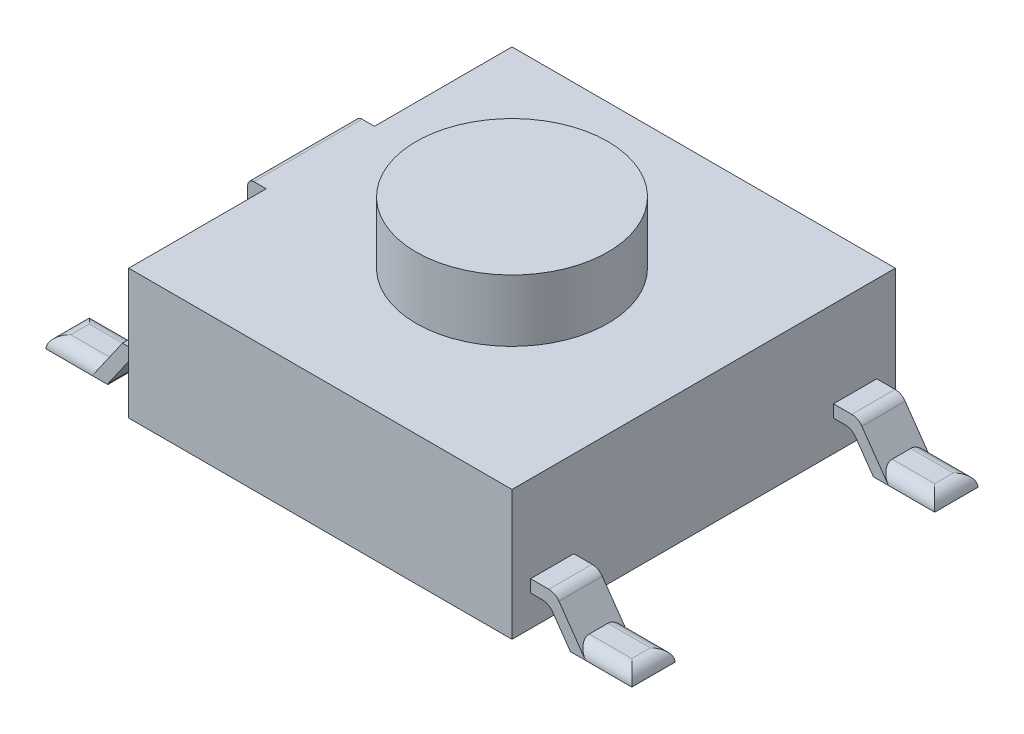
SolidWorks part; units mm, degrees
ref_plane "Plan de face" through (0, 0, 0) normal (0, 0, 1) x (1, 0, 0)
ref_plane "Plan de dessus" through (0, 0, 0) normal (0, 1, 0) x (1, 0, 0)
ref_plane "Plan de droite" through (0, 0, 0) normal (1, 0, 0) x (0, 0, -1)
sketch "Esquisse1" plane through (0, 0, 0) normal (0, 1, 0) x (1, 0, 0)
  line L1 (0, 0) -> (6.2, 0)
  line L2 (0, 0) -> (0, 6.2)
  line L3 (0, 6.2) -> (6.2, 6.2)
  line L4 (6.2, 0) -> (6.2, 6.2)
  dimension "D1" = 6.2
  dimension "D2" = 6.2
extrude "Boss.-Extru.1" add sketch "Esquisse1" along normal blind 2.1
sketch "Esquisse2" plane through (0, 2.1, 0) normal (0, 1, 0) x (1, 0, 0)
  line L0 (0, 6.2) -> (6.2, 0) construction
  line L1 (0, 0) -> (6.2, 6.2) construction
  circle A0 centre (3.1, 3.1) radius 1.55
  dimension "D1" = 3.1
extrude "Boss.-Extru.2" add sketch "Esquisse2" along normal blind 1
sketch "Esquisse3" plane through (0, 0, 0) normal (-1, 0, 0) x (0, 0, 1)
  line L0 (-3.1, 2.1) -> (-3.1, 0) construction
  line L1 (-6.2, 2.1) -> (0, 2.1) construction
  line L2 (-6.2, 0) -> (0, 0) construction
  line L3 (-3.1, 2.1) -> (-3.1, 0) construction
  line L4 (-3.975, 2.1) -> (-2.225, 2.1)
  line L5 (-3.975, 2.1) -> (-3.975, 0)
  line L6 (-3.975, 0) -> (-2.225, 0)
  line L7 (-2.225, 2.1) -> (-2.225, 0)
  dimension "D1" = 1.75
extrude "Boss.-Extru.3" add sketch "Esquisse3" along normal blind 0.3
sketch "Esquisse4" plane through (-0.3, 0, 0) normal (-1, 0, 0) x (0, 0, 1)
  line L0 (-3.1, 2.1) -> (-3.1, 0) construction
  line L1 (-3.55, 0.1) -> (-2.65, 0.1)
  line L2 (-3.55, 0.1) -> (-3.55, 0)
  line L3 (-3.55, 0) -> (-2.65, 0)
  line L4 (-2.65, 0.1) -> (-2.65, 0)
  line L5 (-2.225, 2.1) -> (-3.975, 2.1) construction
  line L6 (-3.1, 0.1) -> (-3.1, 0) construction
  line L7 (-3.975, 0) -> (-2.225, 0) construction
  dimension "D1" = 0.9
  dimension "D2" = 0.1
extrude "Boss.-Extru.4" add sketch "Esquisse4" along normal blind 0.7
fillet "Congé1" radius 0.1 5 edges at (-0.65, 0.1, -3.55) (-0.65, 0.1, -2.65) (-1, 0.1, -3.1) (-0.3, 0.1, -3.1) (-0.3, 2.1, -3.1)
sketch "Esquisse5" plane through (6.2, 0, 0) normal (1, 0, 0) x (0, 0, -1)
  line L0 (0, 2.1) -> (0, 0) construction
  line L1 (0.3, 0.7) -> (1, 0.7)
  line L2 (0.3, 0.7) -> (0.3, 0.5)
  line L3 (0.3, 0.5) -> (1, 0.5)
  line L4 (1, 0.7) -> (1, 0.5)
  line L5 (3.1, 2.1) -> (3.1, 0) construction
  line L6 (0, 2.1) -> (6.2, 2.1) construction
  line L7 (0, 0) -> (6.2, 0) construction
  line L8 (5.2, 0.7) -> (5.2, 0.5)
  line L9 (5.9, 0.7) -> (5.9, 0.5)
  line L10 (5.9, 0.7) -> (5.2, 0.7)
  line L11 (5.9, 0.5) -> (5.2, 0.5)
  dimension "D1" = 0.3
  dimension "D2" = 0.2
  dimension "D3" = 0.7
  dimension "D4" = 0.5
extrude "Boss.-Extru.5" add sketch "Esquisse5" along normal blind 0.4
sketch "Esquisse6" plane through (6.6, 0, 0) normal (1, 0, 0) x (0, 0, -1)
  line L0 (0.3, 0.7) -> (5.9, 0.7) construction
ref_plane "Plan1" through (1.8424, -2.6313, 0) normal (-0.5736, 0.8192, 0) x (0, 0, -1)
sketch "Esquisse7" plane through (1.8424, -2.6313, 0) normal (-0.5736, 0.8192, 0) x (0, 0, -1)
  line L0 (3.1, -5.8079) -> (3.1, -3.7716) construction
  line L1 (5.9, -5.8079) -> (5.2, -5.8079)
  line L2 (5.9, -5.8079) -> (5.9, -5.6079)
  line L3 (5.9, -5.6079) -> (5.2, -5.6079)
  line L4 (5.2, -5.8079) -> (5.2, -5.6079)
  line L5 (0.3, -5.8079) -> (5.9, -5.8079) construction
  line L6 (1, -5.8079) -> (1, -5.6079)
  line L7 (0.3, -5.8079) -> (1, -5.8079)
  line L8 (0.3, -5.8079) -> (0.3, -5.6079)
  line L9 (0.3, -5.6079) -> (1, -5.6079)
  dimension "D1" = 0.7
  dimension "D2" = 0.2
extrude "Boss.-Extru.6" add sketch "Esquisse7" against normal blind 0.7
fillet "Congé2" radius 0.2 4 edges at (6.4959, 0.5, -0.65) (6.4959, 0.5, -5.55) (6.6, 0.7, -5.55) (6.6, 0.7, -0.65)
sketch "Esquisse9" plane through (0, 0, 0) normal (0, 1, 0) x (1, 0, 0)
  line L0 (6.8377, 0.3) -> (6.8377, 1) construction
  line L1 (6.2, 3.1) -> (8.0607, 3.1) construction
  line L2 (6.8377, 1) -> (7.8377, 1)
  line L3 (6.8377, 1) -> (6.8377, 0.3)
  line L4 (6.8377, 0.3) -> (7.8377, 0.3)
  line L5 (7.8377, 1) -> (7.8377, 0.3)
  line L6 (6.2, 0) -> (6.2, 6.2) construction
  line L7 (7.8377, 5.2) -> (7.8377, 5.9)
  line L8 (6.8377, 5.9) -> (7.8377, 5.9)
  line L9 (6.8377, 5.2) -> (6.8377, 5.9)
  line L10 (6.8377, 5.2) -> (7.8377, 5.2)
  dimension "D1" = 1
extrude "Boss.-Extru.7" add sketch "Esquisse9" along normal blind 0.2
fillet "Congé3" radius 0.2 3 edges at (7.8377, 0.2, -0.65) (7.3939, 0.2, -1) (7.3939, 0.2, -0.3)
fillet "Congé4" radius 0.2 3 edges at (7.3939, 0.2, -5.9) (7.8377, 0.2, -5.55) (7.3939, 0.2, -5.2)
sketch "Esquisse10" plane through (0, 0, 0) normal (-1, 0, 0) x (0, 0, 1)
  line L4 (-5.2, 0.5) -> (-5.2, 0.7)
  line L5 (-5.9, 0.5) -> (-5.2, 0.5)
  line L6 (-5.9, 0.7) -> (-5.9, 0.5)
  line L7 (-5.2, 0.7) -> (-5.9, 0.7)
  line L8 (-5.2, 0.5) -> (-5.2, 0.7)
  line L9 (-5.9, 0.5) -> (-5.2, 0.5)
  line L10 (-5.9, 0.7) -> (-5.9, 0.5)
  line L11 (-5.2, 0.7) -> (-5.9, 0.7)
  line L12 (-0.3, 0.7) -> (-1, 0.7)
  line L13 (-1, 0.7) -> (-1, 0.5)
  line L14 (-1, 0.5) -> (-0.3, 0.5)
  line L15 (-0.3, 0.5) -> (-0.3, 0.7)
  line L16 (-0.3, 0.7) -> (-1, 0.7)
  line L17 (-1, 0.7) -> (-1, 0.5)
  line L18 (-1, 0.5) -> (-0.3, 0.5)
  line L19 (-0.3, 0.5) -> (-0.3, 0.7)
  dimension "D1" = 0
  dimension "D2" = 0
extrude "Boss.-Extru.10" add sketch "Esquisse10" along normal blind 0.4
sketch "Esquisse13" plane through (-0.4, 0, 0) normal (-1, 0, 0) x (0, 0, 1)
  line L0 (-5.9, 0.7) -> (-0.3, 0.7) construction
ref_plane "Plan5" through (0.1973, 0.2818, 0) normal (-0.5736, -0.8192, 0) x (0, 0, -1)
sketch "Esquisse14" plane through (0.1973, 0.2818, 0) normal (-0.5736, -0.8192, 0) x (0, 0, -1)
  line L0 (1, -0.6144) -> (1, -0.2868) construction
  line L1 (0.3, -0.7292) -> (1, -0.7292)
  line L2 (0.3, -0.7292) -> (0.3, -0.5292)
  line L3 (0.3, -0.5292) -> (1, -0.5292)
  line L4 (1, -0.7292) -> (1, -0.5292)
  line L5 (3.1, -0.7292) -> (3.1, -0.201) construction
  line L6 (5.9, -0.7292) -> (0.3, -0.7292) construction
  line L7 (5.9, -0.7292) -> (5.9, -0.5292)
  line L8 (5.9, -0.7292) -> (5.2, -0.7292)
  line L9 (5.2, -0.7292) -> (5.2, -0.5292)
  line L10 (5.9, -0.5292) -> (5.2, -0.5292)
  dimension "D1" = 0.2
extrude "Boss.-Extru.11" add sketch "Esquisse14" along normal blind 0.7
sketch "Esquisse16" plane through (0, 0, 0) normal (0, 1, 0) x (1, 0, 0)
  line L1 (-0.6377, 1) -> (-1.6377, 1)
  line L2 (-0.6377, 1) -> (-0.6377, 0.3)
  line L3 (-0.6377, 0.3) -> (-1.6377, 0.3)
  line L4 (-1.6377, 1) -> (-1.6377, 0.3)
  line L5 (-0.6377, 5.2) -> (-1.6377, 5.2)
  line L6 (-0.6377, 5.2) -> (-0.6377, 5.9)
  line L7 (-0.6377, 5.9) -> (-1.6377, 5.9)
  line L8 (-1.6377, 5.2) -> (-1.6377, 5.9)
  dimension "D1" = 1
  dimension "D2" = 0.7
  dimension "D3" = 1
  dimension "D4" = 0.7
extrude "Boss.-Extru.12" add sketch "Esquisse16" along normal blind 0.2
fillet "Congé5" radius 0.2 6 edges at (-1.1939, 0.2, -5.9) (-1.6377, 0.2, -5.55) (-1.1939, 0.2, -5.2) (-1.1939, 0.2, -1) (-1.6377, 0.2, -0.65) (-1.1939, 0.2, -0.3)
